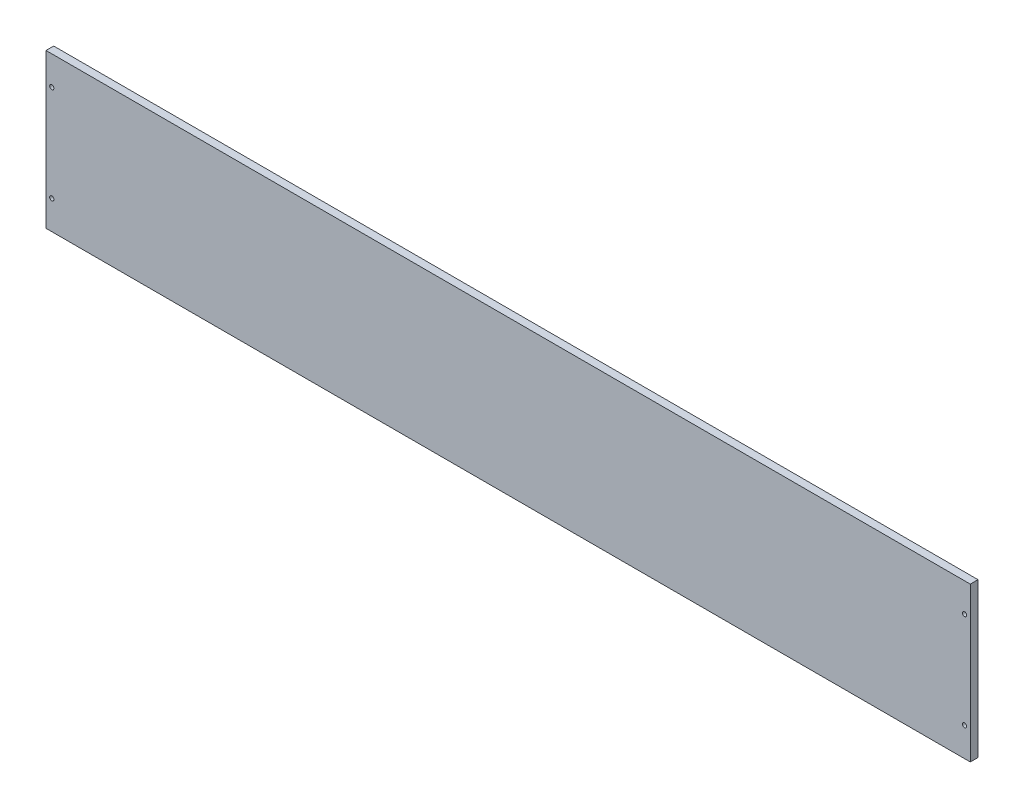
SolidWorks part; units mm, degrees
ref_plane "Plan de face" through (0, 0, 0) normal (0, 0, 1) x (1, 0, 0)
ref_plane "Plan de dessus" through (0, 0, 0) normal (0, 1, 0) x (1, 0, 0)
ref_plane "Plan de droite" through (0, 0, 0) normal (1, 0, 0) x (0, 0, -1)
sketch "Esquisse1" plane through (0, 0, 0) normal (0, 0, 1) x (1, 0, 0)
  line L1 (0, 0) -> (1200, 0)
  line L2 (0, 0) -> (0, -200)
  line L3 (0, -200) -> (1200, -200)
  line L4 (1200, 0) -> (1200, -200)
  dimension "D1" = 200
  dimension "D2" = 1200
extrude "Boss.-Extru.1" add sketch "Esquisse1" along normal blind 10
sketch "Esquisse2" plane through (0, 0, 10) normal (0, 0, 1) x (1, 0, 0)
  line L0 (0, 0) -> (0, -200) construction
  line L1 (1200, -200) -> (1200, 0) construction
  line L2 (1200, 0) -> (0, 0) construction
  line L3 (0, -200) -> (1200, -200) construction
  circle A0 centre (7.5, -37.5) radius 2.75
  circle A1 centre (7.5, -162.5) radius 2.75
  circle A2 centre (1192.5, -37.5) radius 2.75
  circle A3 centre (1192.5, -162.5) radius 2.75
  dimension "D5" = 5.5
  dimension "D6" = 5.5
  dimension "D7" = 5.5
  dimension "D8" = 5.5
  dimension "D1" = 7.5
  dimension "D2" = 7.5
  dimension "D3" = 7.5
  dimension "D4" = 7.5
  dimension "D9" = 37.5
  dimension "D10" = 37.5
  dimension "D11" = 37.5
  dimension "D12" = 37.5
extrude "Enlèv. mat.-Extru.1" cut sketch "Esquisse2" against normal blind 10
chamfer "Chanfrein1" distance 2.5 angle 45 4 edges at (10.25, -162.5, 0) (10.25, -37.5, 0) (1195.25, -37.5, 0) (1195.25, -162.5, 0)
